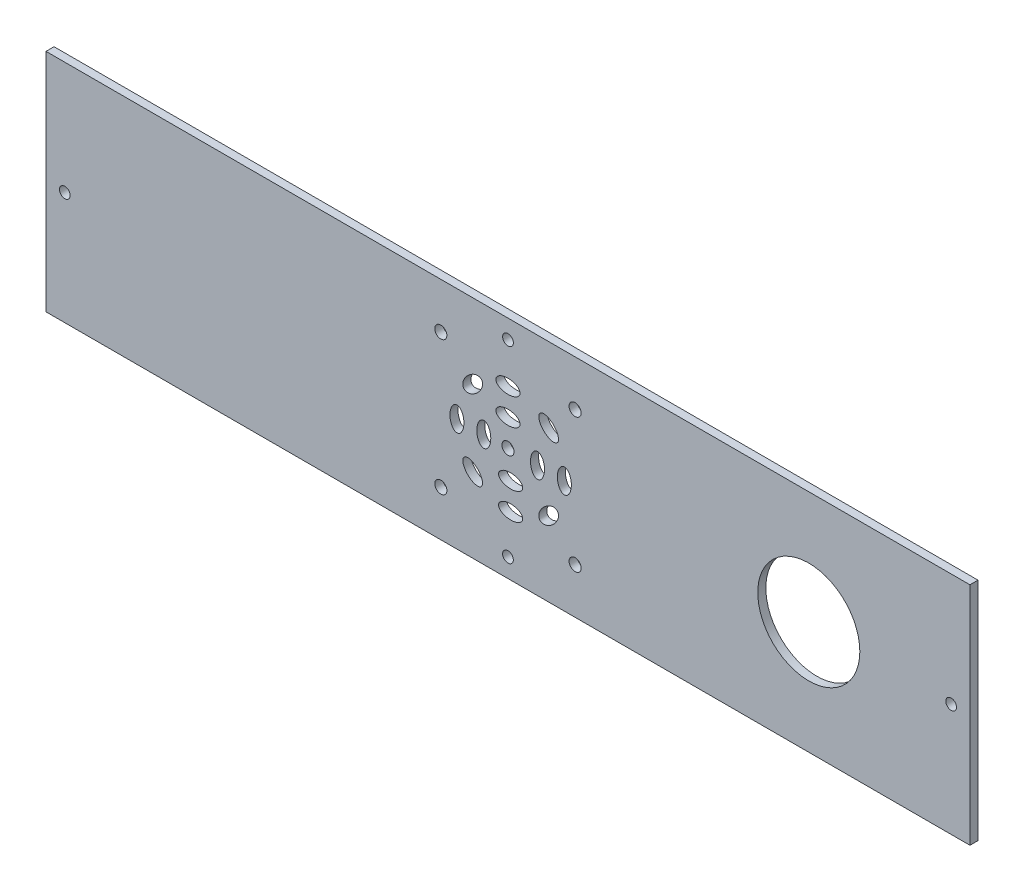
SolidWorks part; units mm, degrees
ref_plane "Piano frontale" through (0, 0, 0) normal (0, 0, 1) x (1, 0, 0)
ref_plane "Piano superiore" through (0, 0, 0) normal (0, 1, 0) x (1, 0, 0)
ref_plane "Piano destro" through (0, 0, 0) normal (1, 0, 0) x (0, 0, -1)
sketch "Schizzo1" plane through (0, 0, 0) normal (0, 0, 1) x (1, 0, 0)
  line L0 (0, 0) -> (0, 84)
  line L1 (0, 84) -> (344, 84)
  line L2 (344, 84) -> (344, 0)
  line L3 (344, 0) -> (0, 0)
  line L4 (0, 42) -> (344, 42) construction
  line L5 (172, 42) -> (172, 123.488) construction
  circle A0 centre (7, 42) radius 2
  circle A1 centre (172, 77) radius 2
  circle A2 centre (172, 7) radius 2
  circle A3 centre (337, 42) radius 2
  circle A4 centre (172, 42) radius 2.25
  circle A5 centre (147, 67) radius 2.25
  circle A6 centre (147, 17) radius 2.25
  circle A7 centre (197, 17) radius 2.25
  circle A8 centre (197, 67) radius 2.25
  circle A9 centre (284, 42) radius 19
  ellipse E0 centre (172, 52) end of major axis (167.5, 52) minor radius 2.6
  ellipse E1 centre (183, 42) end of major axis (183, 37.5) minor radius 2.6
  ellipse E2 centre (173, 32) end of major axis (168.5, 32) minor radius 2.6
  ellipse E3 centre (163, 42) end of major axis (163, 46.5) minor radius 2.6
  ellipse E4 centre (172, 62) end of major axis (167.5, 62) minor radius 2.6
  ellipse E5 centre (187.1421, 56.1421) end of major axis (190.3241, 52.9602) minor radius 2.6
  ellipse E6 centre (193, 42) end of major axis (193, 37.5) minor radius 2.6
  ellipse E7 centre (187.1421, 27.8579) end of major axis (183.9602, 24.6759) minor radius 2.6
  ellipse E8 centre (173, 22) end of major axis (168.5, 22) minor radius 2.6
  ellipse E9 centre (158.8579, 27.8579) end of major axis (155.6759, 31.0398) minor radius 2.6
  ellipse E10 centre (153, 42) end of major axis (153, 46.5) minor radius 2.6
  ellipse E11 centre (158.8579, 56.1421) end of major axis (162.0398, 59.3241) minor radius 2.6
  point P46 (173, 42)
  point P94 (173, 42)
  dimension "D3" = 7
  dimension "D4" = 7
  dimension "D6" = 4
  dimension "D5" = 4.5
  dimension "D16" = 38
  dimension "D1" = 84
  dimension "D2" = 344
  dimension "D7" = 10
  dimension "D8" = 9
  dimension "D9" = 5.2
  dimension "D10" = 10
  dimension "D11" = 9
  dimension "D12" = 5.2
  dimension "D13" = 50
  dimension "D14" = 50
  dimension "D15" = 7
  dimension "D17" = 60
extrude "Estrusione-Estrusione1" add sketch "Schizzo1" along normal blind 3
